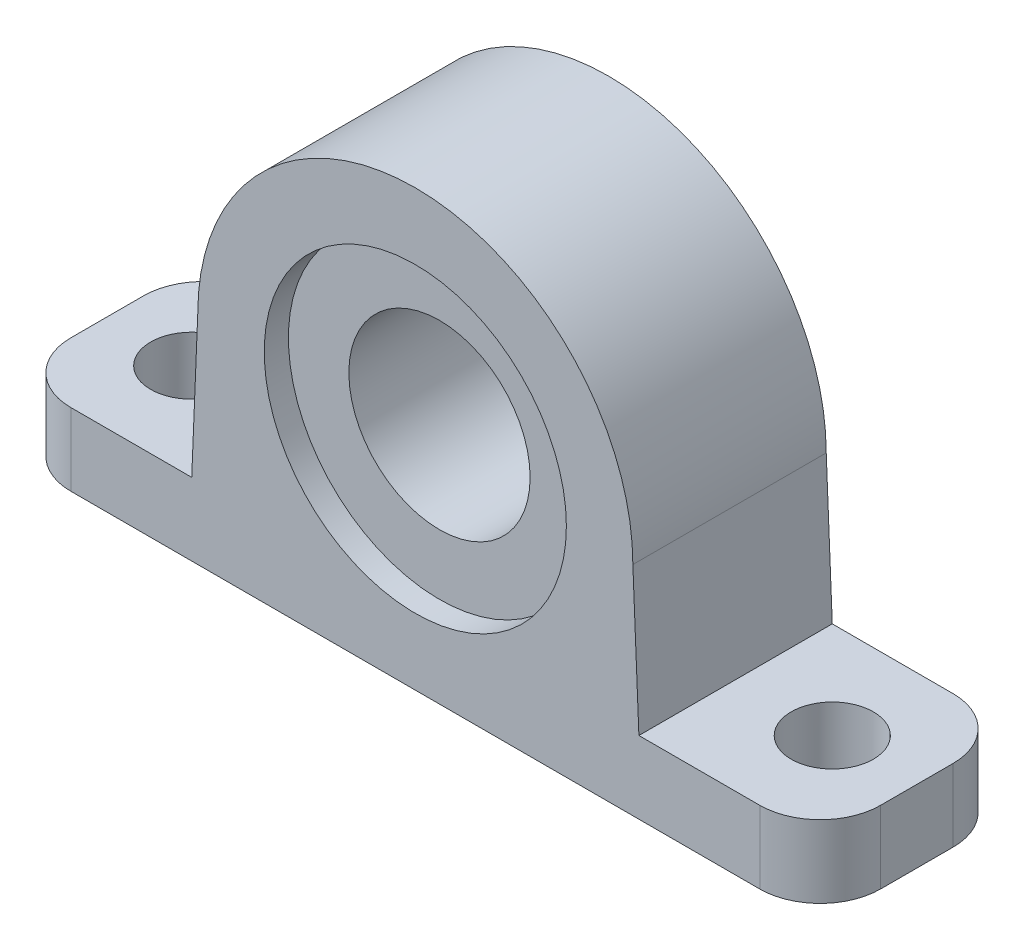
SolidWorks part; units mm, degrees
ref_plane "Ön Düzlem" through (0, 0, 0) normal (0, 0, 1) x (1, 0, 0)
ref_plane "Üst Düzlem" through (0, 0, 0) normal (0, 1, 0) x (1, 0, 0)
ref_plane "Sağ Düzlem" through (0, 0, 0) normal (1, 0, 0) x (0, 0, -1)
sketch "Çizim1" plane through (0, 0, 0) normal (0, 0, 1) x (1, 0, 0)
  line L0 (-24.4437, 1.7785) -> (-39.4437, 1.7785)
  line L1 (-39.4437, 1.7785) -> (-39.4437, -4.2215)
  line L2 (-39.4437, -4.2215) -> (27.5563, -4.2215)
  line L3 (27.5563, -4.2215) -> (27.5563, 1.7785)
  line L4 (27.5563, 1.7785) -> (12.5563, 1.7785)
  line L5 (-5.9437, -4.2215) -> (-5.9437, 52.1565) construction
  line L6 (-23.9437, 13.7785) -> (-24.4437, 1.7785)
  line L7 (12.0563, 13.7785) -> (12.5563, 1.7785)
  circle A0 centre (-5.9437, 13.7785) radius 7.5
  arc A1 (12.0563, 13.7785) -> (-23.9437, 13.7785) centre (-5.9437, 13.7785) ccw
  dimension "D6" = 15
  dimension "D7" = 36
  dimension "D1" = 67
  dimension "D2" = 6
  dimension "D3" = 15
  dimension "D4" = 15
  dimension "D5" = 18
extrude "Yükseklik-Ekstrüzyon1" add sketch "Çizim1" along normal blind 16
sketch "Çizim2" plane through (0, 0, 0) normal (0, 0, 1) x (1, 0, 0)
  circle A0 centre (-5.9437, 13.7785) radius 12.5
  dimension "D1" = 25
extrude "Kes-Ekstrüzyon1" cut sketch "Çizim2" along normal blind 2
sketch "Çizim3" plane through (0, 0, 16) normal (0, 0, 1) x (1, 0, 0)
  circle A0 centre (-5.9437, 13.7785) radius 12.5
  dimension "D1" = 25
extrude "Kes-Ekstrüzyon2" cut sketch "Çizim3" against normal blind 2
sketch "Çizim4" plane through (0, 0, 2) normal (0, 0, -1) x (-1, 0, 0)
  circle A0 centre (5.9437, 13.7785) radius 7.5
  circle A1 centre (5.9437, 13.7785) radius 8.5
  dimension "D1" = 17
  dimension "D2" = 15
extrude "Yükseklik-Ekstrüzyon2" add sketch "Çizim4" along normal blind 5
fillet "Radyus1" radius 5 1 edges at (27.5563, -1.2215, 0)
fillet "Radyus2" radius 5 3 edges at (27.5563, -1.2215, 16) (-39.4437, -1.2215, 16) (-39.4437, -1.2215, 0)
sketch "Çizim5" plane through (0, 0, 0) normal (0, 1, 0) x (1, 0, 0)
  line L0 (-39.4437, -8) -> (27.5563, -8) construction
  line L1 (-39.4437, -11) -> (-39.4437, -5) construction
  line L2 (27.5563, -11) -> (27.5563, -5) construction
  circle A0 centre (-32.4437, -8) radius 3.4
  circle A1 centre (20.5563, -8) radius 3.4
  dimension "D2" = 6.8
  dimension "D3" = 6.8
  dimension "D1" = 53
  dimension "D4" = 7
extrude "Kes-Ekstrüzyon3" cut sketch "Çizim5" against normal blind 16 and the other way blind 35
